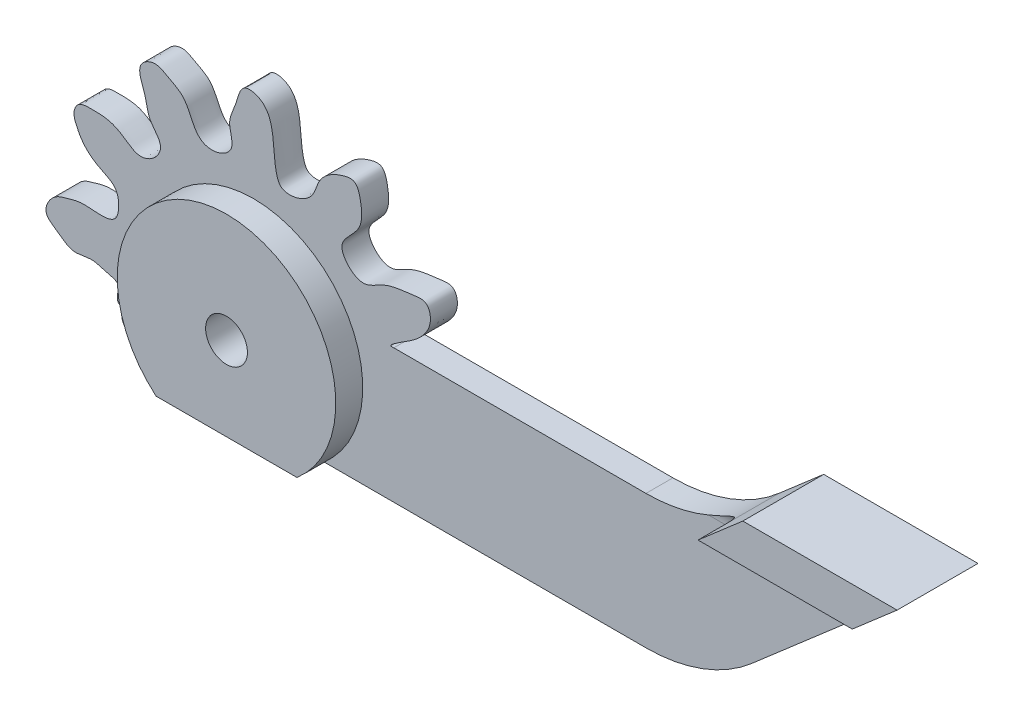
SolidWorks part; units mm, degrees
ref_plane "前视基准面" through (0, 0, 0) normal (0, 0, 1) x (1, 0, 0)
ref_plane "上视基准面" through (0, 0, 0) normal (0, 1, 0) x (1, 0, 0)
ref_plane "右视基准面" through (0, 0, 0) normal (1, 0, 0) x (0, 0, -1)
sketch "草图1" plane through (0, 0, 0) normal (0, 0, 1) x (1, 0, 0)
  line L0 (51.5316, 119.1052) -> (269.5316, 119.1052) construction
  line L1 (64.976, 28.716) -> (112.2137, 28.716)
  line L2 (131.8658, 36.049) -> (140.18, 43.2574)
  line L3 (140.18, 43.2574) -> (168.7965, 43.2574)
  line L4 (168.7965, 43.2574) -> (131.8658, 11.2387)
  line L5 (112.2137, 3.9057) -> (21.5208, 3.9057)
  circle A0 centre (39.4157, 19.407) radius 5.9232
  arc A1 (52.4767, 3.9057) -> (26.3546, 3.9057) centre (39.4157, 19.407) ccw
  arc A2 (112.2137, 28.716) -> (131.8658, 36.049) centre (112.2137, 58.716) ccw
  arc A3 (131.8658, 11.2387) -> (112.2137, 3.9057) centre (112.2137, 33.9057) cw
  spline S0 degree 3 poles (15.2096, 9.9797) (13.2812, 10.3636) (15.5409, 13.6057) (11.8961, 14.1745) (9.4147, 15.2838) (5.8458, 13.9195) (3.3245, 16.1595) (0.1081, 17.9493) (2.0043, 21.6553) (4.8331, 22.4396) (7.7508, 23.234) (10.5511, 22.735) (14.0598, 23.0102) (14.606, 26.0948) (13.9721, 29.0867) (10.5073, 30.3015) (7.9514, 32.346) (6.6272, 34.8129) (5.8368, 36.7719) (6.9062, 39.0385) (9.8987, 39.0454) (12.7362, 38.9952) (15.5409, 37.5004) (18.1575, 35.2645) (21.3931, 36.8883) (22.7711, 40.09) (19.8263, 42.4314) (19.6057, 46.3864) (17.0682, 50.6713) (21.2115, 52.6786) (23.7199, 51.1311) (26.4607, 49.914) (27.8481, 46.8412) (29.3765, 43.7801) (32.9303, 43.3517) (36.2843, 45.6861) (34.3195, 49.7106) (36.3257, 52.9415) (37.019, 57.486) (41.5584, 56.3192) (43.4055, 51.802) (43.0466, 47.7709) (44.383, 43.4742) (47.954, 43.5819) (50.6539, 45.4847) (51.5597, 49.4587) (54.5932, 51.4094) (58.5849, 52.2743) (59.5661, 48.325) (59.6822, 44.0471) (54.9863, 41.2091) (56.7527, 37.5707) (59.8266, 35.4456) (63.8708, 38.4956) (67.5711, 38.7288) (71.747, 39.4082) (72.8306, 35.3228) (69.6894, 32.0103) (67.3772, 30.7156) (64.1194, 28.5242) (65.4493, 28.716) knots 0 0 0 0 0.018083 0.029427 0.044222 0.06346 0.080036 0.095067 0.112886 0.127917 0.141224 0.159056 0.17385 0.188161 0.200964 0.218836 0.240246 0.251297 0.2626 0.271795 0.285102 0.304401 0.316661 0.334441 0.353446 0.362991 0.38416 0.399788 0.426831 0.442771 0.453843 0.471715 0.4877 0.505386 0.521283 0.537873 0.557754 0.577526 0.597754 0.614528 0.632584 0.66992 0.679857 0.696388 0.714648 0.729011 0.756645 0.768188 0.783639 0.807617 0.835445 0.846137 0.865318 0.884867 0.915196 0.92838 0.940606 0.968677 0.986468 1 1 1 1
  spline S1 degree 3 poles (15.2096, 9.9797) (13.8781, 5.4903) (19.4225, 6.0386) (21.5208, 3.9057) knots 0 0 0 0 1 1 1 1
  dimension "D1" = 30
extrude "凸台-拉伸1" add sketch "草图1" along normal blind 5 contours S0 S1 L5 A1 A3 L4 L3 L2 A2 L1 region at (84.8, 24.5237, 0)
sketch "草图2" plane through (0, 0, 5) normal (0, 0, 1) x (1, 0, 0)
  line L0 (52.4767, 3.9057) -> (26.3546, 3.9057)
  arc A0 (52.4767, 3.9057) -> (26.3546, 3.9057) centre (39.4157, 19.407) ccw
  circle A1 centre (39.4157, 19.407) radius 6.6316
extrude "凸台-拉伸2" add sketch "草图2" along normal mid plane 10 separate body contours A0 L0
sketch "草图3" plane through (0, 0, 10) normal (0, 0, 1) x (1, 0, 0)
  circle A0 centre (39.4157, 19.407) radius 3.8774
extrude "切除-拉伸1" cut sketch "草图3" against normal through all
sketch "草图4" plane through (0, 0, 5) normal (0, 0, 1) x (1, 0, 0)
  line L0 (131.8658, 36.049) -> (160.4823, 36.049)
  line L1 (168.7965, 43.2574) -> (131.8658, 11.2387) construction
  line L2 (160.4823, 36.049) -> (168.7965, 43.2574)
  line L3 (168.7965, 43.2574) -> (140.18, 43.2574)
  line L4 (140.18, 43.2574) -> (131.8658, 36.049)
extrude "凸台-拉伸3" add sketch "草图4" along normal blind 10 contours L4 L0 L2 L3
fillet "圆角1" radius 5 1 edges at (146.1741, 36.049, 5)
